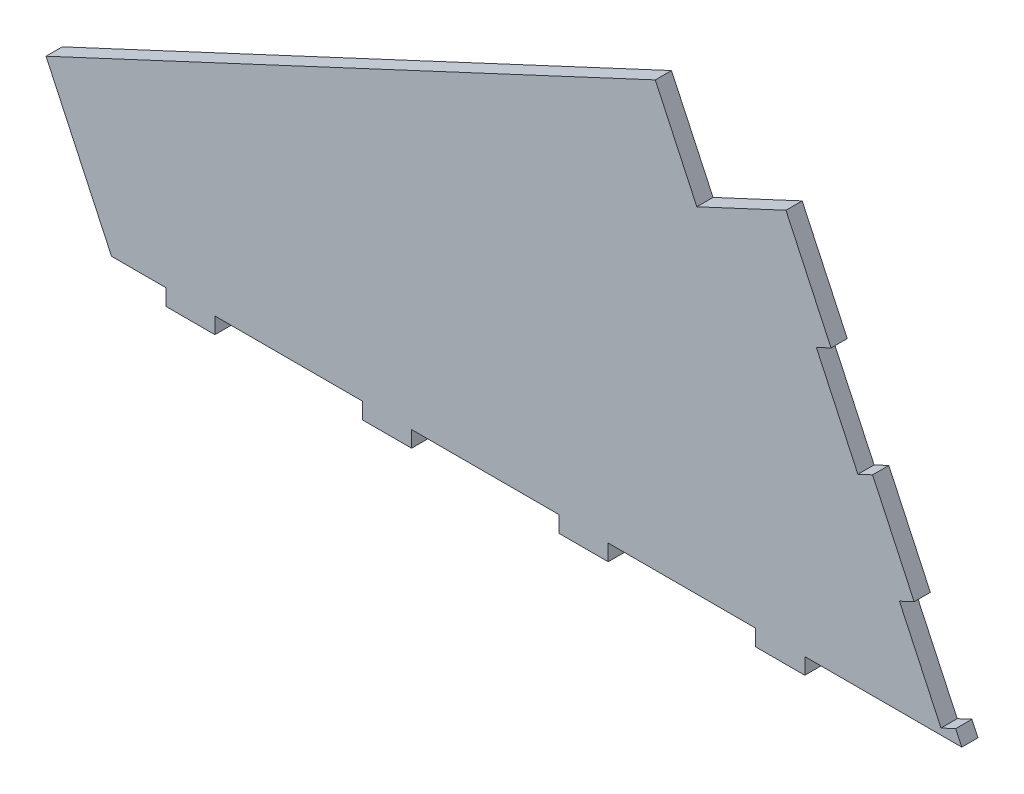
SolidWorks part; units mm, degrees
material "Balsa"
ref_plane "Front Plane" through (0, 0, 0) normal (0, 0, 1) x (1, 0, 0)
ref_plane "Top Plane" through (0, 0, 0) normal (0, 1, 0) x (1, 0, 0)
ref_plane "Right Plane" through (0, 0, 0) normal (1, 0, 0) x (0, 0, -1)
sketch "Sketch1" plane through (0, 0, 0) normal (0, 0, 1) x (1, 0, 0)
  line L0 (321.5462, 12.6346) -> (148.586, 12.6346)
  line L1 (148.586, 12.6346) -> (135.2566, 41.2196)
  line L2 (135.2566, 41.2196) -> (259.1989, 99.0148)
  line L3 (-63.4467, -51.4373) -> (255.5737, 97.3243) construction
  line L4 (259.1989, 99.0148) -> (267.6513, 80.8887)
  line L5 (267.6513, 80.8887) -> (285.7774, 89.341)
  line L6 (285.7774, 89.341) -> (321.5462, 12.6346)
  line L7 (327.4362, 0.0035) -> (398.701, -152.8244) construction
  line L9 (285.7774, 89.341) -> (294.9517, 69.6668) construction
  line L11 (135.2566, 41.2196) -> (148.586, 12.6346) construction
  line L12 (174.6178, 12.6346) -> (194.6178, 12.6346) construction
  point P13 (0, 0)
  point P14 (324.4201, 17.149)
  dimension "D1" = 20
  dimension "D2" = 20
extrude "Boss-Extrude1" add sketch "Sketch1" against normal blind 3.3
sketch "Sketch2" plane through (0, 0, 0) normal (0, 0, 1) x (1, 0, 0)
  line L0 (303.404, 51.5407) -> (294.9517, 69.6668)
  line L1 (303.404, 51.5407) -> (300.4132, 50.146)
  line L2 (294.9517, 69.6668) -> (291.9609, 68.2722)
  line L3 (300.4132, 50.146) -> (291.9609, 68.2722)
  line L4 (320.3088, 15.2883) -> (311.8564, 33.4145)
  line L5 (320.3088, 15.2883) -> (317.3179, 13.8937)
  line L6 (311.8564, 33.4145) -> (308.8656, 32.0199)
  line L7 (317.3179, 13.8937) -> (308.8656, 32.0199)
  dimension "D1" = 3.3
  dimension "D2" = 3.3
extrude "Cut-Extrude1" cut sketch "Sketch2" against normal blind 3.3
sketch "Sketch3" plane through (0, 0, 0) normal (0, 0, 1) x (1, 0, 0)
  line L0 (289.6178, 9.3346) -> (279.6178, 9.3346)
  line L1 (289.6178, 9.3346) -> (289.6178, 13.052)
  line L2 (279.6178, 9.3346) -> (279.6178, 13.052)
  line L3 (289.6178, 13.052) -> (279.6178, 13.052)
  line L4 (249.6178, 9.3346) -> (239.6178, 9.3346)
  line L5 (249.6178, 9.3346) -> (249.6178, 12.9084)
  line L6 (239.6178, 9.3346) -> (239.6178, 12.9084)
  line L7 (249.6178, 12.9084) -> (239.6178, 12.9084)
  line L8 (209.6178, 9.3346) -> (199.6178, 9.3346)
  line L9 (209.6178, 9.3346) -> (209.6178, 13.0454)
  line L10 (199.6178, 9.3346) -> (199.6178, 13.0454)
  line L11 (209.6178, 13.0454) -> (199.6178, 13.0454)
  line L12 (169.6178, 9.3346) -> (159.6178, 9.3346)
  line L13 (169.6178, 9.3346) -> (169.6178, 12.8442)
  line L14 (159.6178, 9.3346) -> (159.6178, 12.8442)
  line L15 (169.6178, 12.8442) -> (159.6178, 12.8442)
extrude "Boss-Extrude2" add sketch "Sketch3" against normal blind 3.3
